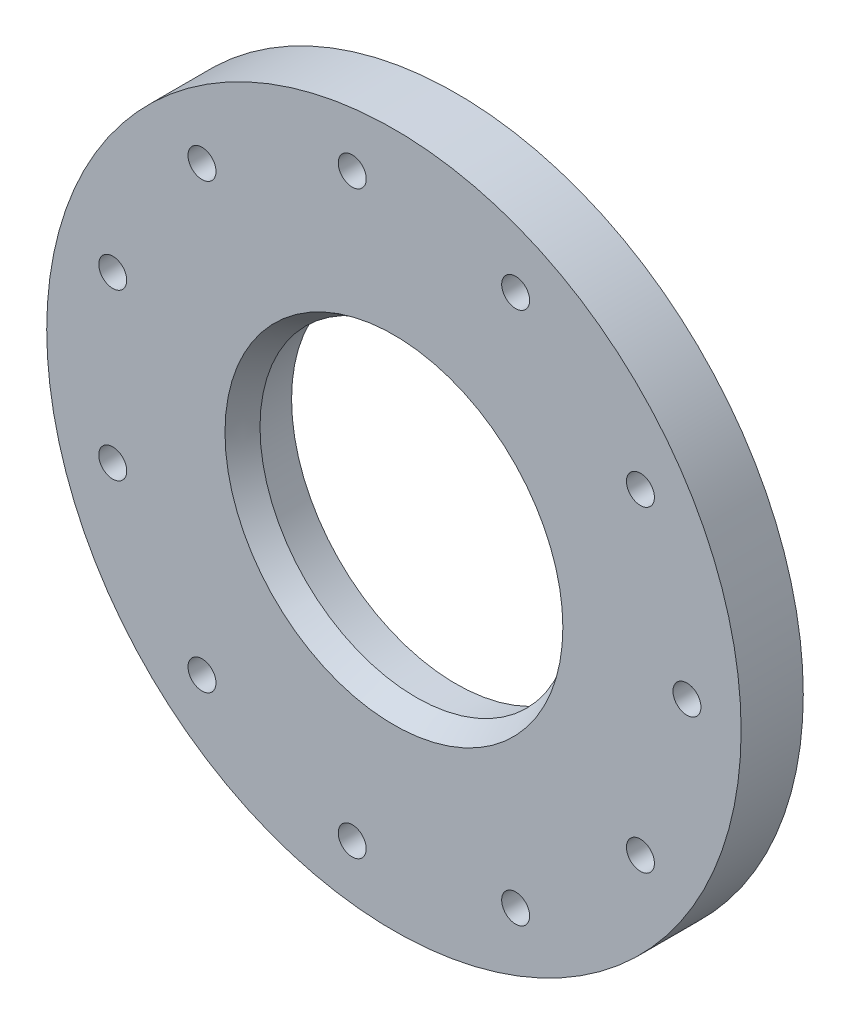
SolidWorks part; units mm, degrees
ref_plane "Front Plane" through (0, 0, 0) normal (0, 0, 1) x (1, 0, 0)
ref_plane "Top Plane" through (0, 0, 0) normal (0, 1, 0) x (1, 0, 0)
ref_plane "Right Plane" through (0, 0, 0) normal (1, 0, 0) x (0, 0, -1)
ref_plane "Plane1" through (0, 0, 15) normal (0, 0, 1) x (1, 0, 0)
sketch "Sketch1" plane through (0, 0, 15) normal (0, 0, 1) x (1, 0, 0)
  circle A0 centre (0, 0) radius 39.1
  circle A1 centre (0, 0) radius 33 construction
  circle A2 centre (33, 0) radius 2.525
  circle A3 centre (27.7614, -17.8411) radius 2.525
  circle A4 centre (13.7087, -30.0179) radius 2.525
  circle A5 centre (-4.6964, -32.6641) radius 2.525
  circle A6 centre (-21.6104, -24.9397) radius 2.525
  circle A7 centre (-31.6633, -9.2972) radius 2.525
  circle A8 centre (-31.6633, 9.2972) radius 2.525
  circle A9 centre (-21.6104, 24.9397) radius 2.525
  circle A10 centre (-4.6964, 32.6641) radius 2.525
  circle A11 centre (13.7087, 30.0179) radius 2.525
  circle A12 centre (27.7614, 17.8411) radius 2.525
  circle A13 centre (0, 0) radius 16.025
  point P28 (0, 0)
extrude "Boss-Extrude1" add sketch "Sketch1" along normal blind 7
sketch "Sketch2" plane through (0, 0, 15) normal (0, 0, -1) x (-1, 0, 0)
  circle A0 centre (0, 0) radius 18.525
  dimension "D1" = 37.05
extrude "Cut-Extrude1" cut sketch "Sketch2" against normal blind 4.5
sketch "Sketch3" plane through (0, 0, 22) normal (0, 0, 1) x (1, 0, 0)
  circle A0 centre (-4.6964, 32.6641) radius 1.575
  circle A1 centre (-4.6964, 32.6641) radius 2.55
  circle A2 centre (13.7087, 30.0179) radius 2.55
  circle A3 centre (13.7087, 30.0179) radius 1.575
  circle A4 centre (27.7614, 17.8411) radius 2.55
  circle A5 centre (27.7614, 17.8411) radius 1.575
  circle A6 centre (33, 0) radius 2.55
  circle A7 centre (33, 0) radius 1.575
  circle A8 centre (27.7614, -17.8411) radius 2.55
  circle A9 centre (27.7614, -17.8411) radius 1.575
  circle A10 centre (13.7087, -30.0179) radius 2.55
  circle A11 centre (13.7087, -30.0179) radius 1.575
  circle A12 centre (-4.6964, -32.6641) radius 2.55
  circle A13 centre (-4.6964, -32.6641) radius 1.575
  circle A14 centre (-21.6104, -24.9397) radius 2.55
  circle A15 centre (-21.6104, -24.9397) radius 1.575
  circle A16 centre (-31.6633, -9.2972) radius 2.55
  circle A17 centre (-31.6633, -9.2972) radius 1.575
  circle A18 centre (-31.6633, 9.2972) radius 2.55
  circle A19 centre (-31.6633, 9.2972) radius 1.575
  circle A20 centre (-21.6104, 24.9397) radius 2.55
  circle A21 centre (-21.6104, 24.9397) radius 1.575
  point P36 (0, 0)
  dimension "D1" = 5.1
  dimension "D2" = 3.15
  dimension "D3" = 11
extrude "Boss-Extrude2" add sketch "Sketch3" against normal blind 4
chamfer "Chamfer1" distance 3 angle 60 1 edges at (16.025, 0, 22) first distance on face at (39.1, 0, 22)
chamfer "Chamfer3" distance 0.5 angle 45 11 edges at (35.525, 0, 15) (30.2864, -17.8411, 15) (16.2337, -30.0179, 15) (-2.1714, -32.6641, 15) (-19.0854, -24.9397, 15) (-29.1383, -9.2972, 15) (-29.1383, 9.2972, 15) (-19.0854, 24.9397, 15) (-2.1714, 32.6641, 15) (16.2337, 30.0179, 15) (30.2864, 17.8411, 15)
equation "\"RingPinShaft\"= 5.05"
equation "\"CenterBearingOut\"=32.05"
equation "\"OutputBearingOut\"=37.05"
equation "\"RingPostIn\"=5.15"
equation "\"CamBearingOut\"=15.1"
equation "\"DiskOutputShaft\"=10.1"
equation "\"CenterShaft\"=25.2"
equation "\"Eccentricity\"=2"
equation "\"CycCamShaft\"=10.05"
equation "\"m3Thru\"=3.15"
equation "\"m3Insert\"=4.2"
equation "\"D2@Sketch3\"=\"m3Thru\""
equation "\"D1@Sketch2\"=\"OutputBearingOut\""
